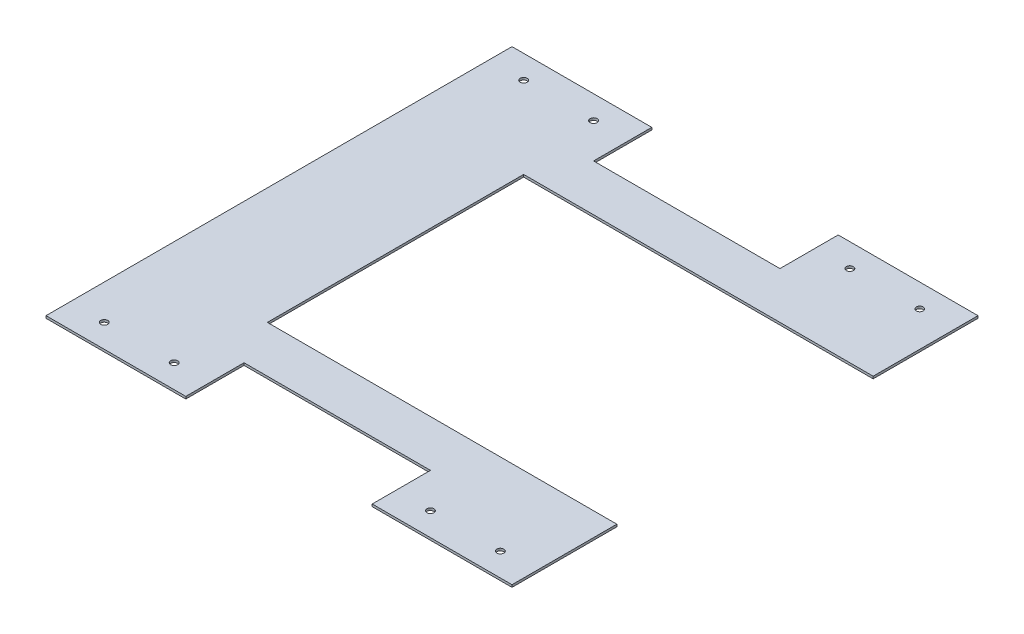
SolidWorks part; units mm, degrees
ref_plane "Plan de face" through (0, 0, 0) normal (0, 0, 1) x (1, 0, 0)
ref_plane "Plan de dessus" through (0, 0, 0) normal (0, 1, 0) x (1, 0, 0)
ref_plane "Plan de droite" through (0, 0, 0) normal (1, 0, 0) x (0, 0, -1)
sketch "Esquisse1" plane through (0, 0, 0) normal (0, 1, 0) x (1, 0, 0)
  line L0 (-40, 100) -> (-40, 75)
  line L1 (40, -100) -> (100, -100)
  line L2 (-100, -100) -> (-100, 100)
  line L3 (40, 100) -> (100, 100)
  line L4 (100, -100) -> (100, -55)
  line L5 (-100, 100) -> (-40, 100)
  line L6 (40, -100) -> (40, -75)
  line L7 (-40, 75) -> (40, 75)
  line L8 (40, 100) -> (40, 75)
  line L9 (-40, -75) -> (40, -75)
  line L10 (-40, -100) -> (-40, -75)
  line L11 (-100, -100) -> (-40, -100)
  line L12 (100, 55) -> (-50, 55)
  line L13 (-50, 55) -> (-50, -55)
  line L14 (100, 0) -> (-100, 0) construction
  line L15 (100, -55) -> (-50, -55)
  line L16 (0, 75) -> (0, 0) construction
  line L17 (100, 100) -> (100, 55)
  circle A0 centre (-85, 90) radius 1.5
  circle A1 centre (-55, 90) radius 1.5
  circle A2 centre (-55, -90) radius 1.5
  circle A3 centre (-85, -90) radius 1.5
  circle A4 centre (55, -90) radius 1.5
  circle A5 centre (85, -90) radius 1.5
  circle A34 centre (55, 90) radius 1.5
  circle A35 centre (85, 90) radius 1.5
  point P10 (0, 75)
  point P35 (-50, 0)
  dimension "D11" = 55
  dimension "D12" = 50
  dimension "D13" = 100
  dimension "D4" = 30
  dimension "D5" = 90
  dimension "D3" = 3
  dimension "D7" = 3
  dimension "D8" = 90
  dimension "D1" = 55
  dimension "D2" = 100
  dimension "D6" = 40
  dimension "D9" = 100
  dimension "D10" = 25
extrude "Boss.-Extru.1" add sketch "Esquisse1" along normal blind 1
